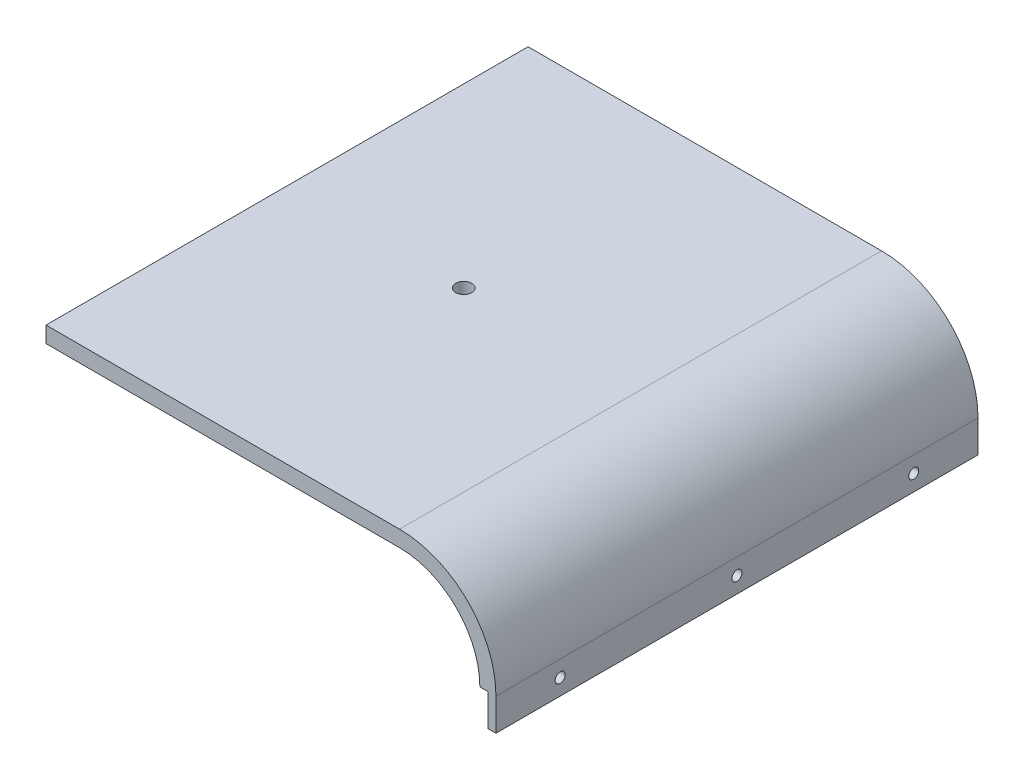
SolidWorks part; units mm, degrees
ref_plane "Front Plane" through (0, 0, 0) normal (0, 0, 1) x (1, 0, 0)
ref_plane "Top Plane" through (0, 0, 0) normal (0, 1, 0) x (1, 0, 0)
ref_plane "Right Plane" through (0, 0, 0) normal (1, 0, 0) x (0, 0, -1)
sketch "Sketch1" plane through (0, 0, 0) normal (0, 0, 1) x (1, 0, 0)
  line L0 (-139.7, 0) -> (139.7, 0)
  line L1 (139.7, 0) -> (139.7, -152.4) construction
  line L2 (139.7, -76.2) -> (215.9, -76.2) construction
  line L3 (-139.7, -12.7) -> (139.7, -12.7)
  line L4 (-139.7, 0) -> (-139.7, -12.7)
  line L5 (215.9, -76.2) -> (203.2, -76.2)
  circle A0 centre (139.7, -76.2) radius 76.2 construction
  arc A1 (139.7, 0) -> (215.9, -76.2) centre (139.7, -76.2) cw
  arc A2 (139.7, -12.7) -> (203.2, -76.2) centre (139.7, -76.2) cw
  point P4 (0, 0)
  dimension "D1" = 152.4
  dimension "D2" = 355.6
  dimension "D3" = 12.7
extrude "Boss-Extrude1" add sketch "Sketch1" along normal blind 190.5 and the other way blind 190.5
sketch "Sketch2" plane through (0, -76.2, 0) normal (0, -1, 0) x (1, 0, 0)
  line L0 (203.2, 190.5) -> (215.9, 190.5) construction
  line L1 (209.55, 190.5) -> (215.9, 190.5)
  line L2 (209.55, 190.5) -> (209.55, -190.5)
  line L3 (209.55, -190.5) -> (215.9, -190.5)
  line L4 (215.9, 190.5) -> (215.9, -190.5)
extrude "Boss-Extrude2" add sketch "Sketch2" along normal blind 25.4
sketch "Sketch3" plane through (215.9, 0, 0) normal (1, 0, 0) x (0, 0, -1)
  line L0 (-190.5, -88.9) -> (190.5, -88.9) construction
  line L1 (-190.5, -101.6) -> (-190.5, -76.2) construction
  line L2 (190.5, -101.6) -> (190.5, -76.2) construction
  line L3 (0, -76.2) -> (0, -101.6) construction
  line L4 (190.5, -76.2) -> (-190.5, -76.2) construction
  line L5 (190.5, -101.6) -> (-190.5, -101.6) construction
  line L6 (139.7, -76.2) -> (139.7, -101.6) construction
  line L7 (-139.7, -76.2) -> (-139.7, -101.6) construction
  circle A0 centre (-139.7, -88.9) radius 3.9687
  circle A1 centre (0, -88.9) radius 3.9687
  circle A2 centre (139.7, -88.9) radius 3.9687
  dimension "D3" = 7.9375
  dimension "D1" = 139.7
  dimension "D2" = 139.7
extrude "Cut-Extrude1" cut sketch "Sketch3" against normal blind 25.4
sketch "Sketch4" plane through (0, 0, 0) normal (0, 1, 0) x (1, 0, 0)
  circle A0 centre (0, 0) radius 6.35
  dimension "D1" = 12.7
extrude "Cut-Extrude2" cut sketch "Sketch4" against normal blind 17.78
